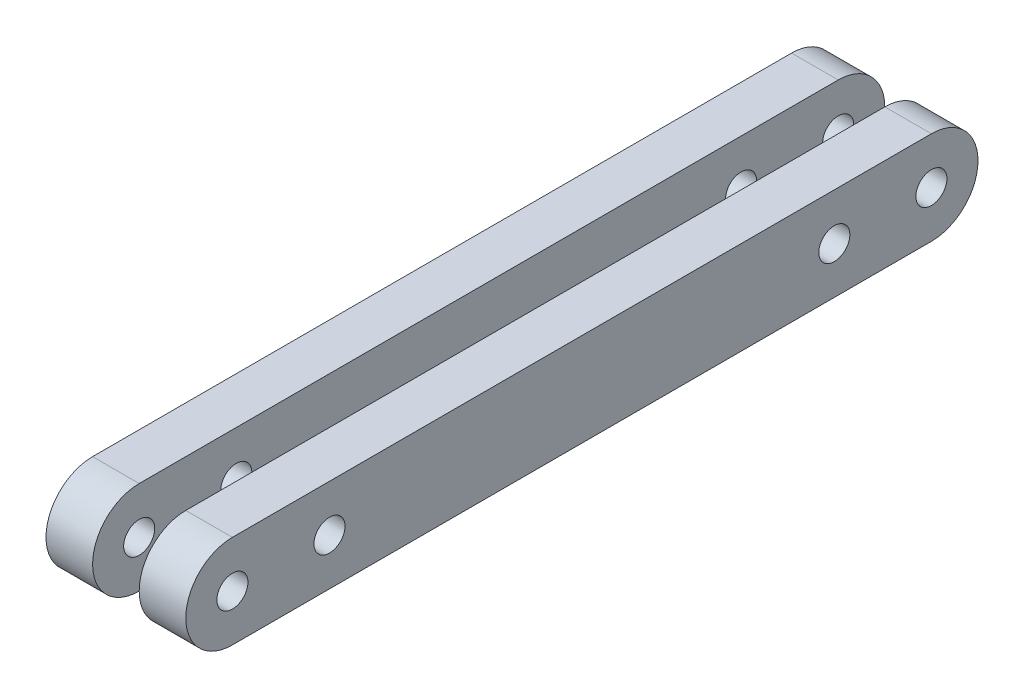
SolidWorks part; units mm, degrees
ref_plane "Front Plane" through (0, 0, 0) normal (0, 0, 1) x (1, 0, 0)
ref_plane "Top Plane" through (0, 0, 0) normal (0, 1, 0) x (1, 0, 0)
ref_plane "Right Plane" through (0, 0, 0) normal (1, 0, 0) x (0, 0, -1)
sketch "length (ref to equation file)" plane through (0, 0, 0) normal (1, 0, 0) x (0, 0, -1)
  line L0 (0, 0) -> (90, 0)
  dimension "D1" = 90
ref_axis "pivot w/ link 1" through (0, 0, 0) along (1, 0, 0)
ref_axis "pivot w/ platform" through (0, 0, -90) along (1, 0, 0)
ref_plane "Plane1" through (3, 0, 0) normal (1, 0, 0) x (0, 0, -1)
sketch "Sketch1" plane through (3, 0, 0) normal (1, 0, 0) x (0, 0, -1)
  line L0 (0, 0) -> (90, 0) construction
  line L1 (0, 6) -> (90, 6)
  line L2 (0, -6) -> (90, -6)
  arc A0 (0, 6) -> (0, -6) centre (0, 0) ccw
  arc A1 (90, -6) -> (90, 6) centre (90, 0) ccw
  point P4 (45, 0)
  dimension "D1" = 12
extrude "Boss-Extrude1" add sketch "Sketch1" along normal blind 6 contours L2 A1 L1 A0
sketch "Sketch2" plane through (9, 0, 0) normal (1, 0, 0) x (0, 0, -1)
  circle A0 centre (0, 0) radius 2
  circle A2 centre (90, 0) radius 2
  circle A5 centre (0, 0) radius 2 construction
extrude "Cut-Extrude1" cut sketch "Sketch2" against normal through all and the other way through all
mirror "Mirror4" about plane through (0, 0, 0) normal (1, 0, 0) of bodies 103
sketch "Sketch3" plane through (3, 0, 0) normal (1, 0, 0) x (0, 0, -1)
  line L0 (0, 0) -> (90, 0) construction
  line L1 (12.5, 0) -> (77.5, 0)
  line L2 (0, 6) -> (90, 6) construction
  line L3 (12.5, 6) -> (77.5, 6)
  line L4 (12.5, 6) -> (12.5, -6)
  line L5 (12.5, -6) -> (77.5, -6)
  line L6 (77.5, 6) -> (77.5, -6)
  line L7 (0, -6) -> (90, -6) construction
  point P5 (45, 0)
  point P7 (45, 0)
  line M14 (0, 6) -> (90, 6)
  line M16 (90, -6) -> (0, -6)
  dimension "D1" = 65
extrude "Boss-Extrude2" [suppressed] add sketch "Sketch3" against normal up to surface (6 mm away) contours L6 L4 M14 M16 up to face at (-3, 0, -2)
sketch "Sketch5" plane through (9, 0, 0) normal (1, 0, 0) x (0, 0, -1)
  point P0 (77.5, 0)
  point P2 (12.5, 0)
hole_wizard "Ø4.0mm Dowel Hole1" positions "Sketch5" profile "Sketch6" hole size "Ø4.0" standard "ANSI Metric" end condition through all
sketch "Sketch6" plane through (9, 0, -77.5) normal (0, 1, 0) x (0, 0, -1)
  line L0 (0, 0) -> (0, 18)
  line L1 (0, 18) -> (2, 18)
  line L2 (2, 18) -> (2, 0)
  line L5 (2, 0) -> (0, 0)
  line L11 (0, -6.35) -> (0, 107.95) construction
  dimension "Thru Hole Dia." = 4
  dimension "Thru Hole Depth" = 18
equation "\"link 2\"= 90mm"
equation "\"D1@length (ref to equation file)\" = \"link 2\""
equation "\"link 1 thickness\" = 6mm"
equation "\"beam width\" = 30mm"
equation "\"beam side wall thickness\" = 3mm"
equation "\"D1@Plane1\" = \"link 2 plane\""
equation "\"link 2 plane\"= \"link 1 thickness\" / 2"
equation "\"motor center z\" = 60mm"
equation "\"motor center y\" = 20mm"
equation "\"link 1\" = 40mm"
equation "\"pivot height\"= 140mm"
equation "\"beam length\" = 120mm"
equation "\"camera height\" = 250mm"
equation "\"link height\" = 12mm"
equation "\"D1@Sketch1\"=\"link height\""
equation "\"D1@Boss-Extrude1\"=\"link 1 thickness\""
